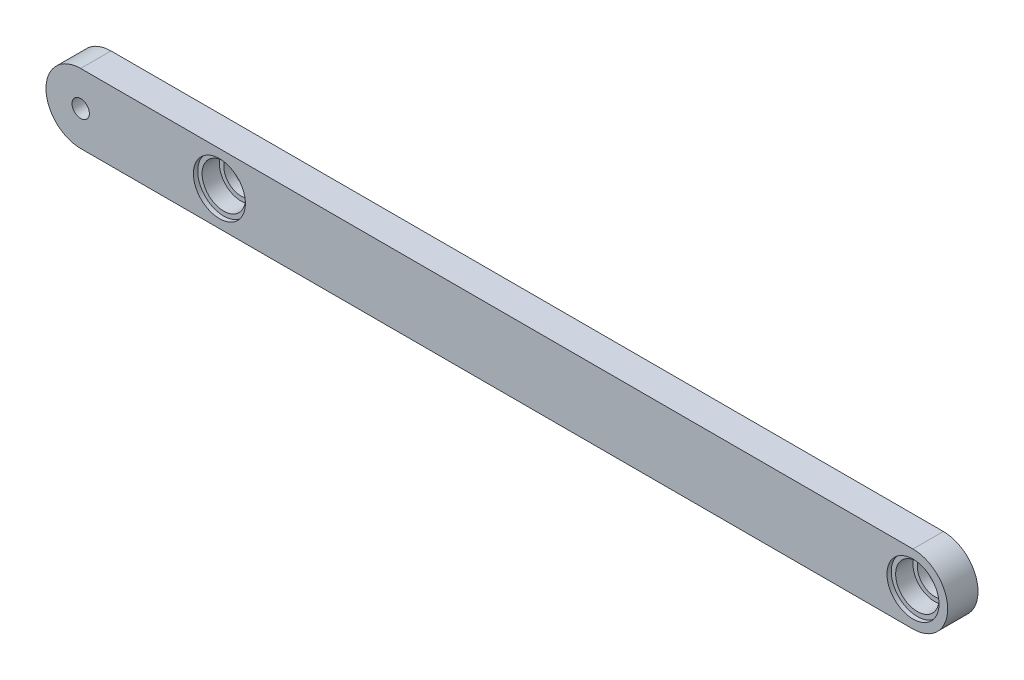
SolidWorks part; units mm, degrees
ref_plane "前视基准面" through (0, 0, 0) normal (0, 0, 1) x (1, 0, 0)
ref_plane "上视基准面" through (0, 0, 0) normal (0, 1, 0) x (1, 0, 0)
ref_plane "右视基准面" through (0, 0, 0) normal (1, 0, 0) x (0, 0, -1)
sketch "草图1" plane through (0, 0, 0) normal (0, 0, 1) x (1, 0, 0)
  line L1 (0, 4) -> (100, 4)
  line L2 (0, -4) -> (100, -4)
  arc A0 (0, 4) -> (0, -4) centre (0, 0) ccw
  arc A1 (100, -4) -> (100, 4) centre (100, 0) ccw
  point P4 (100, 0)
  dimension "D2" = 8
  dimension "D3" = 8
  dimension "D1" = 100
extrude "凸台-拉伸1" add sketch "草图1" along normal blind 3.5
sketch "草图2" plane through (0, 0, 3.5) normal (0, 0, 1) x (1, 0, 0)
  circle A0 centre (100, 0) radius 3
  circle A1 centre (100, 0) radius 2.5
  circle A2 centre (100, 0) radius 2
  dimension "D1" = 6
  dimension "D2" = 5
  dimension "D3" = 4
extrude "切除-拉伸1" cut sketch "草图2" against normal through all contours A2 region at (100, 0, 3.5)
extrude "切除-拉伸2" cut sketch "草图2<3>" against normal blind 2.5 contours A1 A2 region at (97.5707, 0, 3.5)
sketch "草图2<3>" plane through (0, 0, 3.5) normal (0, 0, 1) x (1, 0, 0) same geometry as "草图2"
extrude "切除-拉伸3" cut sketch "草图2<4>" against normal blind 0.5 contours A0 A1 region at (97.0849, 0, 3.5)
sketch "草图2<4>" plane through (0, 0, 3.5) normal (0, 0, 1) x (1, 0, 0) same geometry as "草图2"
sketch "草图3" plane through (0, 0, 3.5) normal (0, 0, 1) x (1, 0, 0)
  line L0 (20, 0) -> (4, 0)
  circle A2 centre (20, 0) radius 3
  circle A3 centre (20, 0) radius 2.5
  circle A4 centre (20, 0) radius 2
  point P9 (100, 0)
  dimension "D2" = 6
  dimension "D3" = 5
  dimension "D4" = 4
  dimension "D1" = 16
  dimension "D5" = 80
extrude "切除-拉伸4" cut sketch "草图3" against normal through all contours A4 region at (20, 1.9434, 3.5)
extrude "切除-拉伸5" cut sketch "草图3<3>" against normal blind 2.5 contours A4 A3 region at (20, 2.4293, 3.5)
sketch "草图3<3>" plane through (0, 0, 3.5) normal (0, 0, 1) x (1, 0, 0) same geometry as "草图3"
extrude "切除-拉伸6" cut sketch "草图3<4>" against normal blind 0.5 contours A3 A2 region at (20, 2.9151, 3.5)
sketch "草图3<4>" plane through (0, 0, 3.5) normal (0, 0, 1) x (1, 0, 0) same geometry as "草图3"
sketch "草图5" plane through (0, 0, 3.5) normal (0, 0, 1) x (1, 0, 0)
  line L0 (20, 0) -> (4, 0)
  circle A0 centre (4, 0) radius 1
  dimension "D2" = 2
  dimension "D1" = 16
extrude "切除-拉伸8" cut sketch "草图5" against normal through all contours A0 region at (3.0283, 0, 3.5)
sketch "草图6" plane through (0, 0, 3.5) normal (0, 0, 1) x (1, 0, 0)
  line L0 (0, 4) -> (4, 4)
  line L1 (0, -4) -> (4, -4)
  arc A0 (4, 4) -> (4, -4) centre (4, 0) ccw
  arc A1 (0, 4) -> (0, -4) centre (0, 0) ccw
extrude "切除-拉伸9" cut sketch "草图6" against normal through all
